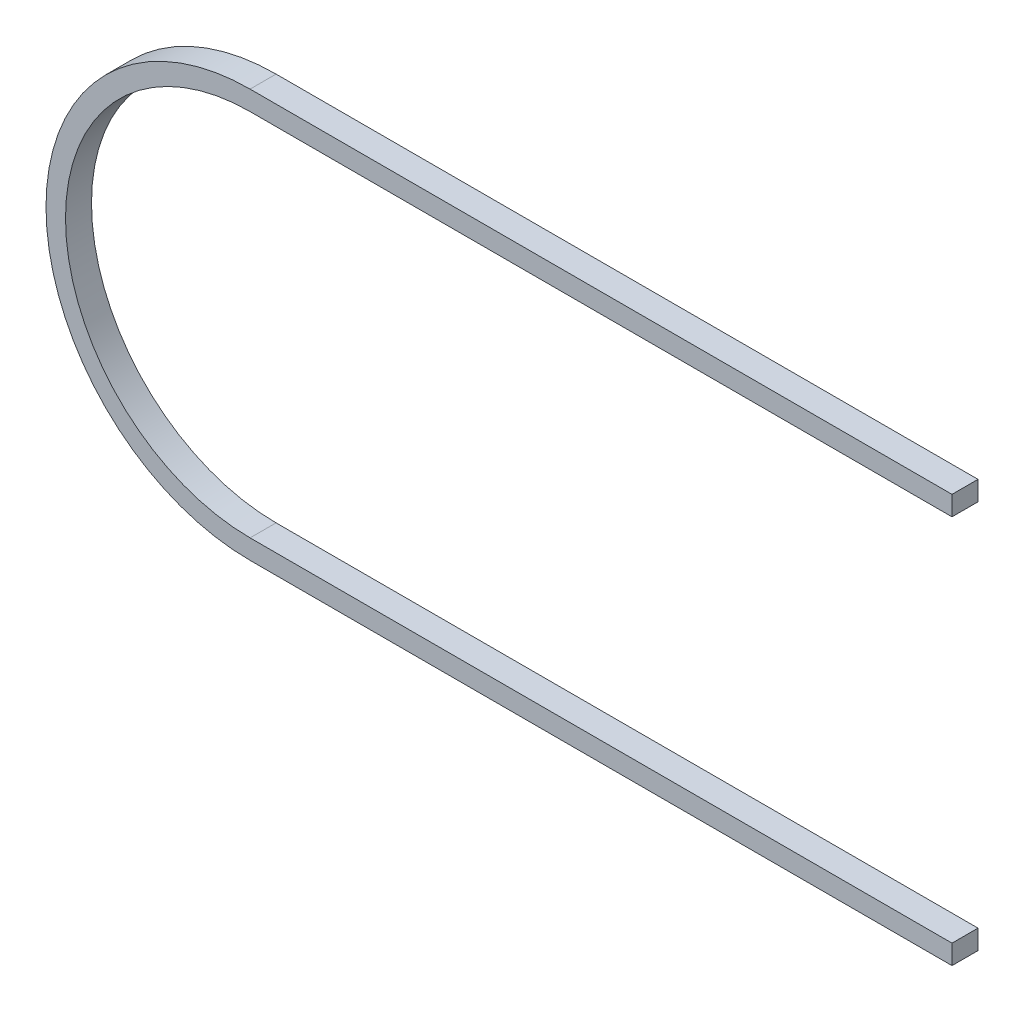
SolidWorks part; units mm, degrees
ref_plane "Front Plane" through (0, 0, 0) normal (0, 0, 1) x (1, 0, 0)
ref_plane "Top Plane" through (0, 0, 0) normal (0, 1, 0) x (1, 0, 0)
ref_plane "Right Plane" through (0, 0, 0) normal (1, 0, 0) x (0, 0, -1)
sketch "Sketch1" plane through (0, 0, 0) normal (0, 0, 1) x (1, 0, 0)
  line L0 (0, 19.939) -> (68.58, 19.939)
  line L1 (0, 18.034) -> (68.58, 18.034)
  line L2 (68.58, 18.034) -> (68.58, 19.939)
  line L3 (0, -18.034) -> (68.58, -18.034)
  line L4 (68.58, -18.034) -> (68.58, -19.939)
  line L5 (68.58, -19.939) -> (0, -19.939)
  arc A0 (0, 19.939) -> (0, -19.939) centre (0, 0) ccw
  arc A1 (0, 18.034) -> (0, -18.034) centre (0, 0) ccw
  dimension "D1" = 68.58
  dimension "D2" = 1.905
  dimension "D3" = 36.068
extrude "Boss-Extrude1" add sketch "Sketch1" along normal blind 2.54
